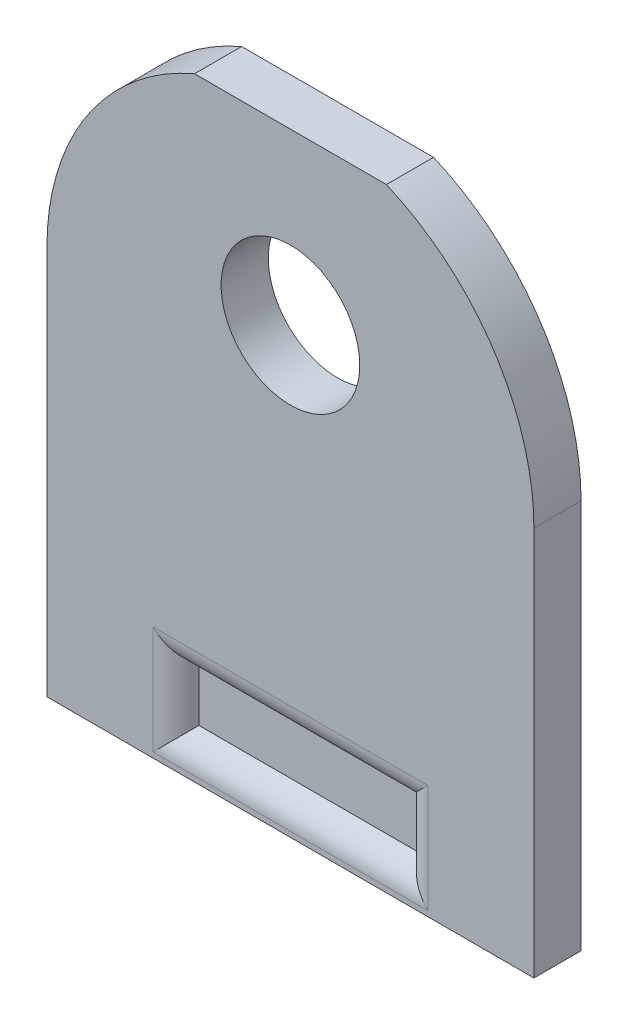
SolidWorks part; units mm, degrees
ref_plane "Front Plane" through (0, 0, 0) normal (0, 0, 1) x (1, 0, 0)
ref_plane "Top Plane" through (0, 0, 0) normal (0, 1, 0) x (1, 0, 0)
ref_plane "Right Plane" through (0, 0, 0) normal (1, 0, 0) x (0, 0, -1)
sketch "Sketch1" plane through (0, 0, 0) normal (0, 0, 1) x (1, 0, 0)
  line L1 (0, 0) -> (17.56, 0)
  line L2 (0, 0) -> (0, 6.55)
  line L3 (0, 6.55) -> (17.56, 6.55)
  line L4 (17.56, 0) -> (17.56, 6.55)
  circle A0 centre (8.78, 8.5) radius 2.5
  arc A3 (17.56, 6.55) -> (0, 6.55) centre (8.78, 6.55) ccw
  dimension "D3" = 1.95
  dimension "D4" = 5
  dimension "D1" = 17.56
  dimension "D2" = 6.55
extrude "Boss-Extrude1" add sketch "Sketch1" along normal blind 1.7
sketch "Sketch3" plane through (0, 0, 1.7) normal (0, 0, 1) x (1, 0, 0)
  line L6 (0, 6.55) -> (0, 0)
  line L7 (0, 0) -> (17.56, 0)
  line L8 (17.56, 0) -> (17.56, 6.55)
  line L11 (0, 6.55) -> (0, 0)
  line L12 (0, 0) -> (17.56, 0)
  line L13 (17.56, 0) -> (17.56, 6.55)
  line L15 (0, 0) -> (17.56, 0)
  line L16 (17.56, 6.55) -> (17.56, 0)
  line L17 (0, 0) -> (0, 6.55)
  line L18 (5.32, 14.6195) -> (12.24, 14.6195)
  arc A1 (17.56, 6.55) -> (0, 6.55) centre (8.78, 6.55) ccw
  arc A2 (17.56, 6.55) -> (0, 6.55) centre (8.78, 6.55) ccw
  arc A9 (17.56, 6.55) -> (12.24, 14.6195) centre (8.78, 6.55) ccw
  arc A10 (0, 6.55) -> (5.32, 14.6195) centre (8.78, 6.55) cw
  arc M33 (17.56, 6.55) -> (0, 6.55) centre (8.78, 6.55) ccw
  dimension "D1" = 0
extrude "Cut-Extrude4" cut sketch "Sketch3" against normal through all contours L18 M33
sketch "Sketch6" plane through (0, 0, 0) normal (0, -1, 0) x (1, 0, 0)
  line L4 (0, 0) -> (17.56, 0)
  line L5 (17.56, 0) -> (17.56, 1.7)
  line L6 (17.56, 1.7) -> (0, 1.7)
  line L7 (0, 1.7) -> (0, 0)
  line L8 (0, 0) -> (17.56, 0)
  line L9 (17.56, 0) -> (17.56, 1.7)
  line L10 (17.56, 1.7) -> (0, 1.7)
  line L11 (0, 1.7) -> (0, 0)
  dimension "D1" = 0
extrude "Boss-Extrude4" add sketch "Sketch6" along normal blind 7.5
sketch "Sketch9" plane through (0, 0, 1.7) normal (0, 0, 1) x (1, 0, 0)
  line L0 (12.78, -4.3532) -> (17.56, -4.3532) construction
  line L1 (12.78, -6.3532) -> (4.78, -6.3532)
  line L2 (12.78, -6.3532) -> (12.78, -4.3532)
  line L3 (12.78, -4.3532) -> (4.78, -4.3532)
  line L4 (4.78, -6.3532) -> (4.78, -4.3532)
  line L6 (4.78, -4.3532) -> (0, -4.3532) construction
  line L8 (17.56, -7.5) -> (17.56, 6.55) construction
  line L9 (0, -7.5) -> (0, 6.55) construction
  dimension "D1" = 2
  dimension "D2" = 8
extrude "Cut-Extrude2" cut sketch "Sketch9" against normal blind 0.7
fillet "Fillet1" radius 1 4 edges at (12.78, -5.3532, 1.7) (8.78, -6.3532, 1.7) (4.78, -5.3532, 1.7) (8.78, -4.3532, 1.7)
